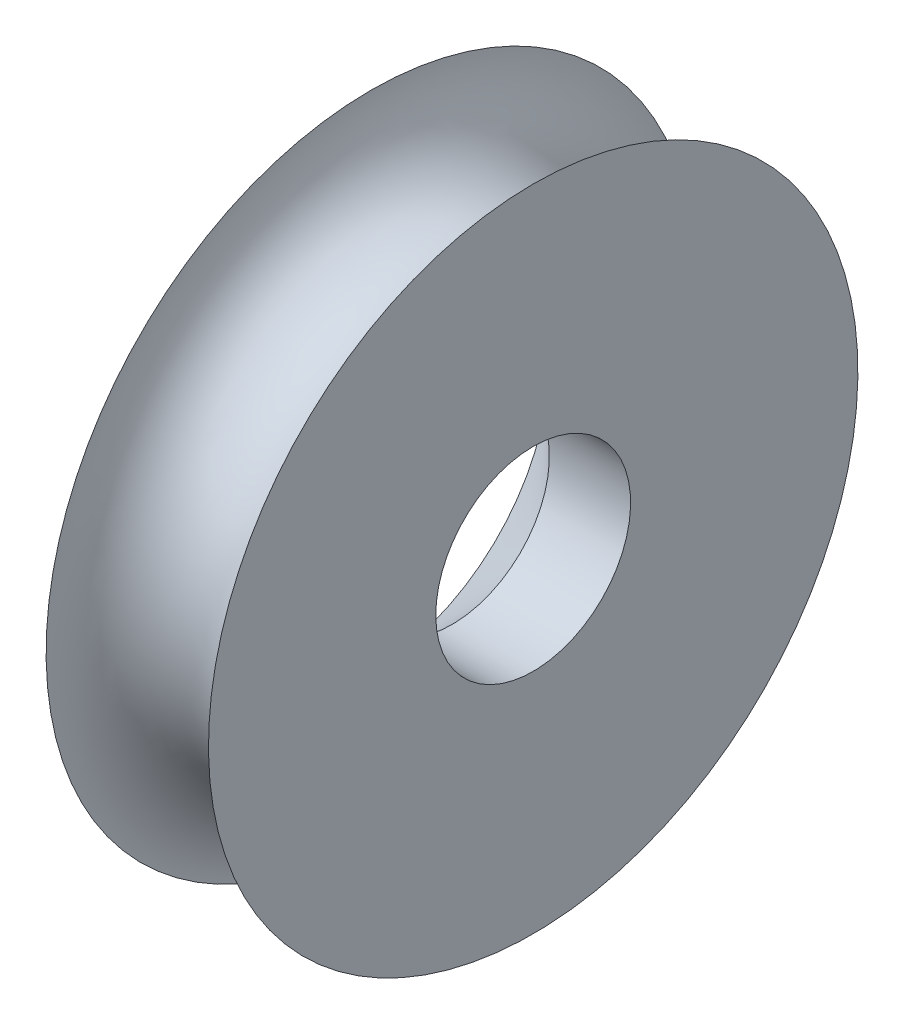
SolidWorks part; units mm, degrees
ref_plane "Ebene vorne" through (0, 0, 0) normal (0, 0, 1) x (1, 0, 0)
ref_plane "Ebene oben" through (0, 0, 0) normal (0, 1, 0) x (1, 0, 0)
ref_plane "Ebene rechts" through (0, 0, 0) normal (1, 0, 0) x (0, 0, -1)
sketch "Skizze1" plane through (0, 0, 0) normal (0, 0, 1) x (1, 0, 0)
  line L0 (0, 0) -> (0, 4)
  line L1 (0, 0) -> (-2, 0)
  line L2 (-2, 0) -> (-2, 4)
  arc A0 (-2, 4) -> (0, 4) centre (-1, 4) ccw
revolve "Rotation1" add sketch "Skizze1" angle 360 about L1
hole_wizard "Formsenkung für M2 Linsensenkschraube mit Schlitz1" positions "Skizze4" profile "Skizze6" countersink size "M2" standard "ISO"
sketch "Skizze4" plane through (-2, 0, 0) normal (-1, 0, 0) x (0, 0, 1)
  point P0 (0, 0)
sketch "Skizze6" plane through (-2, 0, 0) normal (0, 1, 0) x (0, 0, 1)
  line L0 (0, 0) -> (0, 5.721)
  line L1 (0, 5.721) -> (1.2, 5)
  line L2 (1.2, 5) -> (1.2, 1)
  line L3 (1.2, 1) -> (2.2, 0)
  line L5 (2.2, 0) -> (0, 0)
  line L6 (-1.2, 1) -> (-2.2, 0) construction
  line L10 (0, 5.721) -> (-1.2, 5) construction
  line L11 (0, -6.35) -> (0, 107.95) construction
  dimension "Bohrerdurchmesser" = 2.4
  dimension "Bohrungstiefe" = 5
  dimension "Senkdurchmesser (Oben)" = 4.4
  dimension "Senkwinkel (Oben)" = 90
  dimension "Spitzenwinkel" = 118
